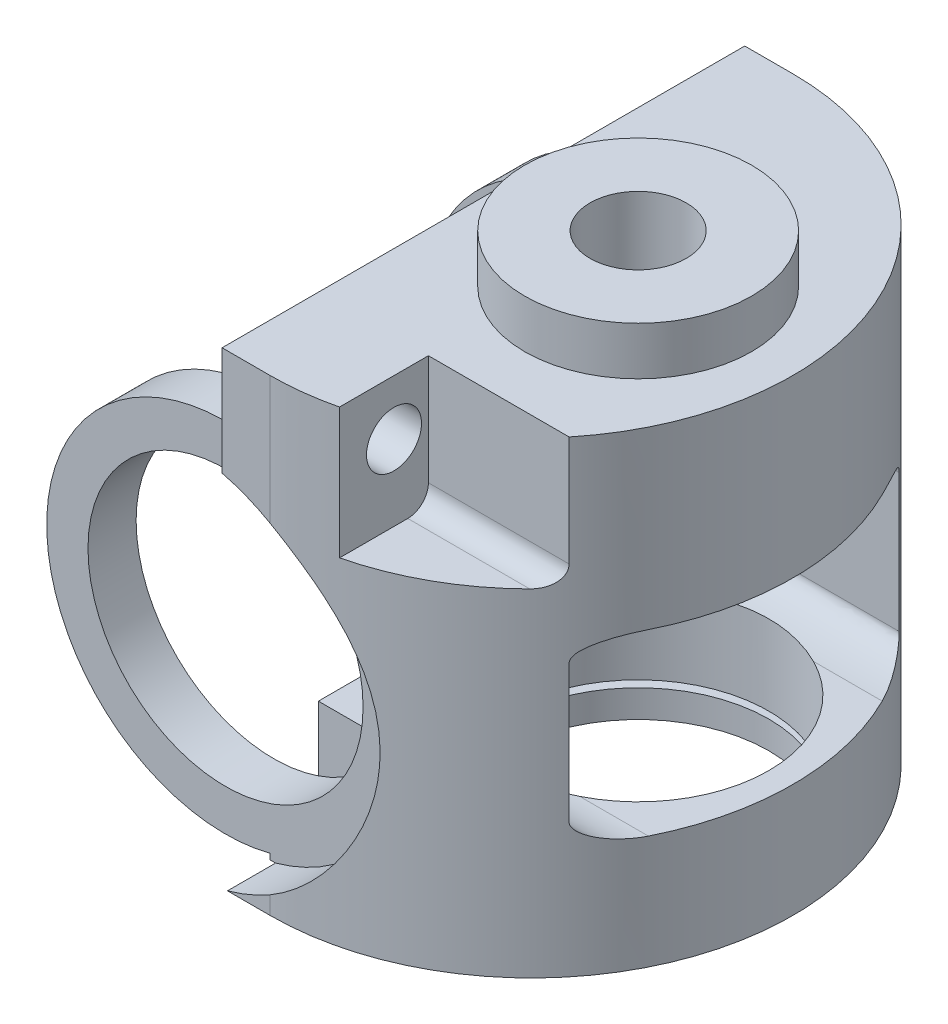
SolidWorks part; units mm, degrees
ref_plane "Plan de face" through (0, 0, 0) normal (0, 0, 1) x (1, 0, 0)
ref_plane "Plan de dessus" through (0, 0, 0) normal (0, 1, 0) x (1, 0, 0)
ref_plane "Plan de droite" through (0, 0, 0) normal (1, 0, 0) x (0, 0, -1)
sketch "Sketch2" plane through (0, 0, 0) normal (0, 1, 0) x (1, 0, 0)
  line L0 (-3.5, -19) -> (-3.5, 19)
  line L1 (-3.5, 19) -> (0, 19)
  line L2 (-3.5, -19) -> (0, -19)
  line L3 (19, 0) -> (19, 16.5672) construction
  arc A0 (0, -19) -> (0, 19) centre (0, 0) ccw
  circle A1 centre (7.75, 0) radius 3.5
  point P7 (-3.5, 0)
  dimension "D1" = 19
  dimension "D3" = 22.5
  dimension "D4" = 11.25
  dimension "D5" = 7
  dimension "D2" = 38
extrude "Boss-Extrude1" add sketch "Sketch2" along normal blind 34
sketch "Sketch19" plane through (0, 34, 0) normal (0, 1, 0) x (1, 0, 0)
  circle A0 centre (7.75, 0) radius 8.25
  circle A1 centre (7.75, 0) radius 3.5
  dimension "D1" = 16.5
  dimension "D2" = 7
extrude "Boss-Extrude3" add sketch "Sketch19" along normal blind 3.5
sketch "Sketch7" plane through (0, 0, 19) normal (0, 0, -1) x (-1, 0, 0)
  line L0 (6.75, 13) -> (0, 0) construction
  circle A3 centre (6.75, 13) radius 13.5
  point P0 (0, 0)
  dimension "D1" = 13
  dimension "D2" = 6.75
  dimension "D3" = 27
extrude "Cut-Extrude4" cut sketch "Sketch7" along normal blind 3.5 contours A3
sketch "Sketch25" plane through (0, 0, 15.5) normal (0, 0, 1) x (1, 0, 0)
  circle A0 centre (-6.75, 13) radius 13
  dimension "D1" = 26
extrude "Boss-Extrude4" add sketch "Sketch25" against normal blind 3.5
sketch "Sketch27" plane through (0, 0, 15.5) normal (0, 0, 1) x (1, 0, 0)
  circle A0 centre (-6.75, 13) radius 10
  dimension "D1" = 20
extrude "Cut-Extrude13" cut sketch "Sketch27" against normal up to surface (3.5 mm away) up to face at (-11.625, 13, 12)
pattern_linear "LPattern3" count 2 spacing 34.5 along (0, 0, -1) of "Cut-Extrude4"
pattern_linear "LPattern4" count 2 spacing 27.5 along (0, 0, -1) of "Boss-Extrude4", "Cut-Extrude13"
sketch "Sketch6" plane through (-3.5, 0, 0) normal (1, 0, 0) x (0, 0, -1)
  line L0 (15.5, 0) -> (-15.5, 0) construction
  line L1 (12, 21.25) -> (-12, 21.25)
  line L2 (12, 21.25) -> (12, 8.25)
  line L3 (12, 8.25) -> (-12, 8.25)
  line L4 (-12, 21.25) -> (-12, 8.25)
  point P1 (0, 8.25)
  point P6 (0, 0)
  point P7 (11, 8.25)
  point P8 (11, 8.481)
  dimension "D1" = 8.25
  dimension "D2" = 13
  dimension "D3" = 24
extrude "Cut-Extrude3" cut sketch "Sketch6" along normal through all
fillet "Fillet2" radius 3.5 2 edges at (8.3904, 8.25, -12) (6.8161, 21.25, -12) second distance 1.5 first distance on face at (7.75, 8.25, 3.5) first distance on face at (7.75, 21.25, -3.5)
fillet "Fillet3" radius 3.5 2 edges at (8.3904, 8.25, 12) (6.8161, 21.25, 12) second distance 1.5 first distance on face at (7.75, 8.25, 3.5) first distance on face at (7.75, 21.25, -3.5)
sketch "Sketch16" plane through (-3.5, 0, 0) normal (-1, 0, 0) x (0, 0, 1)
  line L1 (-19, 34) -> (19, 34) construction
  line L2 (-19, 34) -> (-19, 26.103) construction
  point P0 (-11, 31.5)
  dimension "D1" = 8
  dimension "D2" = 2.5
hole_wizard "M2 Tapped Hole1" positions "Sketch16" profile "Sketch15" tap size "M2" standard "ISO"
sketch "Sketch15" plane through (-3.5, 31.5, -11) normal (0, 1, 0) x (0, 0, 1)
  line L0 (0, 0) -> (0, 5.9807)
  line L1 (0, 5.9807) -> (0.8, 5.5)
  line L2 (0.8, 5.5) -> (0.8, 0)
  line L5 (0.8, 0) -> (0, 0)
  line L10 (0, 5.9807) -> (-0.8, 5.5) construction
  line L11 (0, -6.35) -> (0, 107.95) construction
  dimension "Tap Drill Dia." = 1.6
  dimension "Tap Drill Depth" = 5.5
  dimension "Drill Angle" = 118
cosmetic thread "Hole Thread1" parameters "D1"=4.5, "D2"=2
sketch "Sketch17" plane through (-3.5, 0, 0) normal (-1, 0, 0) x (0, 0, 1)
  line L1 (-19, 34) -> (19, 34) construction
  line L2 (19, 34) -> (19, 26.103) construction
  circle A1 centre (14.5, 30) radius 2
  dimension "D1" = 4
  dimension "D2" = 4.5
  dimension "D3" = 4
extrude "Cut-Extrude5" cut sketch "Sketch17" against normal blind 8
sketch "Sketch18" plane through (4.5, 0, 0) normal (-1, 0, 0) x (0, 0, 1)
  line L0 (12, 34) -> (14.5, 30) construction
  line L6 (0, 0) -> (0, 34) construction
  line L7 (-15.5, 0) -> (15.5, 0) construction
  line L8 (12, 26) -> (12, 34)
  line L9 (19, 34) -> (12, 34)
  line L10 (19, 24.5) -> (19, 34)
  line L11 (19, 24.5) -> (13.5, 24.5)
  arc A3 (12, 26) -> (13.5, 24.5) centre (13.5, 26) ccw
  dimension "D1" = 7
  dimension "D2" = 9.5
  dimension "D3" = 1.5
  dimension "D4" = 4
  dimension "D5" = 8
  dimension "D6" = 5.5
  dimension "D7" = 2.5
extrude "Cut-Extrude6" cut sketch "Sketch18" against normal up to next
sketch "Sketch20" plane through (0, 21.25, 0) normal (0, -1, 0) x (1, 0, 0)
  circle A0 centre (7.75, 0) radius 9.75
  dimension "D1" = 19.5
extrude "Cut-Extrude7" cut sketch "Sketch20" against normal blind 6.25
sketch "Sketch21" plane through (0, 27.5, 0) normal (0, -1, 0) x (1, 0, 0)
  circle A0 centre (7.75, 0) radius 8.5
  dimension "D1" = 17
extrude "Cut-Extrude8" cut sketch "Sketch21" against normal blind 0.5
sketch "Sketch22" plane through (0, 8.25, 0) normal (0, 1, 0) x (1, 0, 0)
  circle A0 centre (7.75, 0) radius 9.5
  dimension "D1" = 19
extrude "Cut-Extrude9" cut sketch "Sketch22" against normal blind 5.75 and the other way blind 1
sketch "Sketch23" plane through (0, 2.5, 0) normal (0, 1, 0) x (1, 0, 0)
  circle A0 centre (7.75, 0) radius 10.5
  dimension "D1" = 21
extrude "Cut-Extrude10" cut sketch "Sketch23" against normal blind 0.5
sketch "Sketch24" plane through (0, 2, 0) normal (0, 1, 0) x (1, 0, 0)
  circle A0 centre (7.75, 0) radius 9.5
  dimension "D1" = 19
extrude "Cut-Extrude11" cut sketch "Sketch24" against normal blind 2
